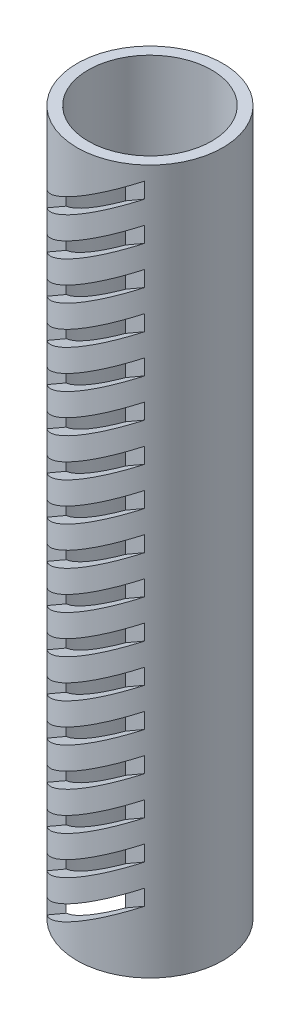
SolidWorks part; units mm, degrees
material "PBT General Purpose"
ref_plane "Front Plane" through (0, 0, 0) normal (0, 0, 1) x (1, 0, 0)
ref_plane "Top Plane" through (0, 0, 0) normal (0, 1, 0) x (1, 0, 0)
ref_plane "Right Plane" through (0, 0, 0) normal (1, 0, 0) x (0, 0, -1)
sketch "Sketch1" plane through (0, 0, 0) normal (0, 1, 0) x (1, 0, 0)
  circle A0 centre (0, 0) radius 25.654
  circle A1 centre (0, 0) radius 21.717
  dimension "D1" = 51.308
  dimension "D2" = 43.434
extrude "Boss-Extrude1" add sketch "Sketch1" along normal blind 247.65
ref_axis "Axis1" through (0, 247.65, 0) along (0, -1, 0)
sketch "Sketch2" plane through (0, 0, 0) normal (0, 0, 1) x (1, 0, 0)
  line L0 (25.654, 247.65) -> (-25.654, 247.65) construction
  line L1 (0, 0) -> (0, 247.65) construction
  line L3 (-28.0352, 216.6525) -> (-25.654, 212.5281)
  line L4 (-25.654, 212.5281) -> (28.0352, 243.5256)
  line L5 (28.0352, 243.5256) -> (25.654, 247.65)
  line L6 (25.654, 247.65) -> (-28.0352, 216.6525)
  line L7 (-25.654, 247.65) -> (-25.654, 0) construction
  line L10 (25.654, 0) -> (25.654, 247.65) construction
  dimension "D1" = 60
  dimension "D2" = 4.7625
  dimension "D4" = 0
extrude "Cut-Extrude1" cut sketch "Sketch2" along normal blind 12.7 from offset 19.05
pattern_linear "LPattern1" count 17 spacing 13.462 along (0, -1, 0) of "Cut-Extrude1"
sketch "Sketch5" plane through (0, 247.65, 0) normal (0, 1, 0) x (1, 0, 0)
  circle A0 centre (0, 0) radius 22.86
  dimension "D1" = 45.72
extrude "Cut-Extrude3" [suppressed] cut sketch "Sketch5" against normal blind 5.08 contours A0
